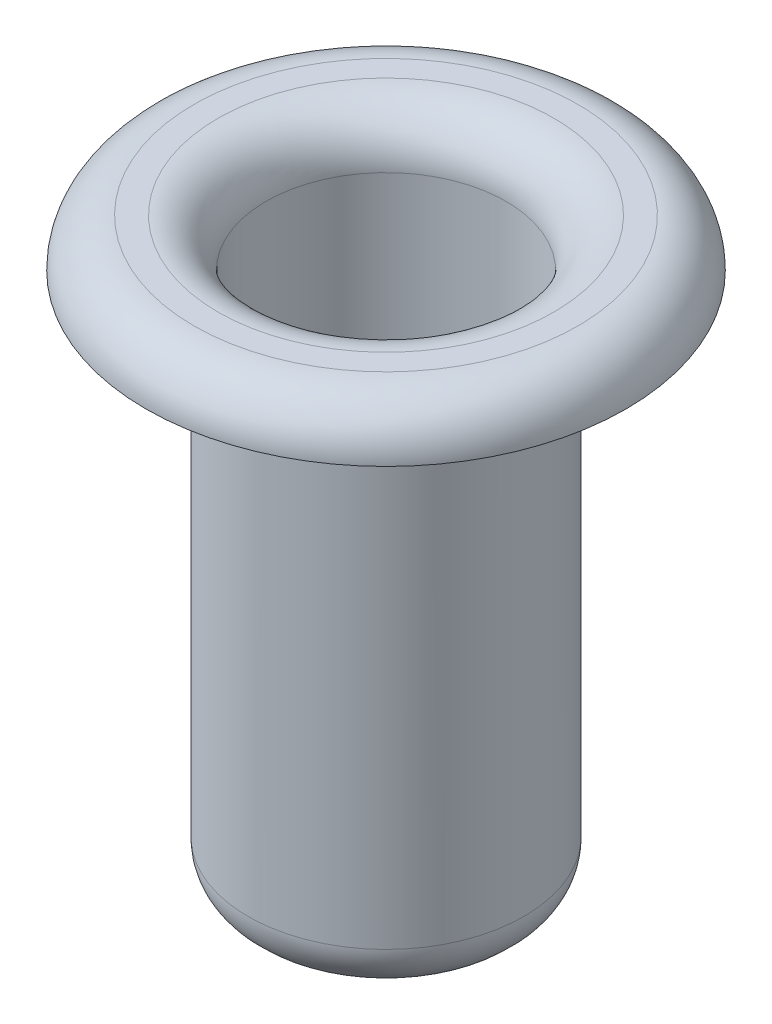
SolidWorks part; units mm, degrees
ref_plane "Front Plane" through (0, 0, 0) normal (0, 0, 1) x (1, 0, 0)
ref_plane "Top Plane" through (0, 0, 0) normal (0, 1, 0) x (1, 0, 0)
ref_plane "Right Plane" through (0, 0, 0) normal (1, 0, 0) x (0, 0, -1)
sketch "Sketch1" plane through (0, 0, 0) normal (0, 1, 0) x (1, 0, 0)
  circle A0 centre (0, 0) radius 1.4605
  dimension "D1" = 2.921
extrude "Boss-Extrude1" add sketch "Sketch1" along normal blind 5.588
sketch "Sketch2" plane through (0, 5.588, 0) normal (0, 1, 0) x (1, 0, 0)
  circle A0 centre (0, 0) radius 2.54
  dimension "D1" = 5.08
extrude "Boss-Extrude2" add sketch "Sketch2" along normal blind 0.508
sketch "Sketch3" plane through (0, 6.096, 0) normal (0, 1, 0) x (1, 0, 0)
  circle A0 centre (0, 0) radius 1.27
  dimension "D1" = 2.54
extrude "Cut-Extrude1" cut sketch "Sketch3" against normal through all
fillet "Fillet1" radius 0.508 3 edges at (0, 0, 1.4605) (0, 6.096, 2.54) (0, 6.096, 1.27)
